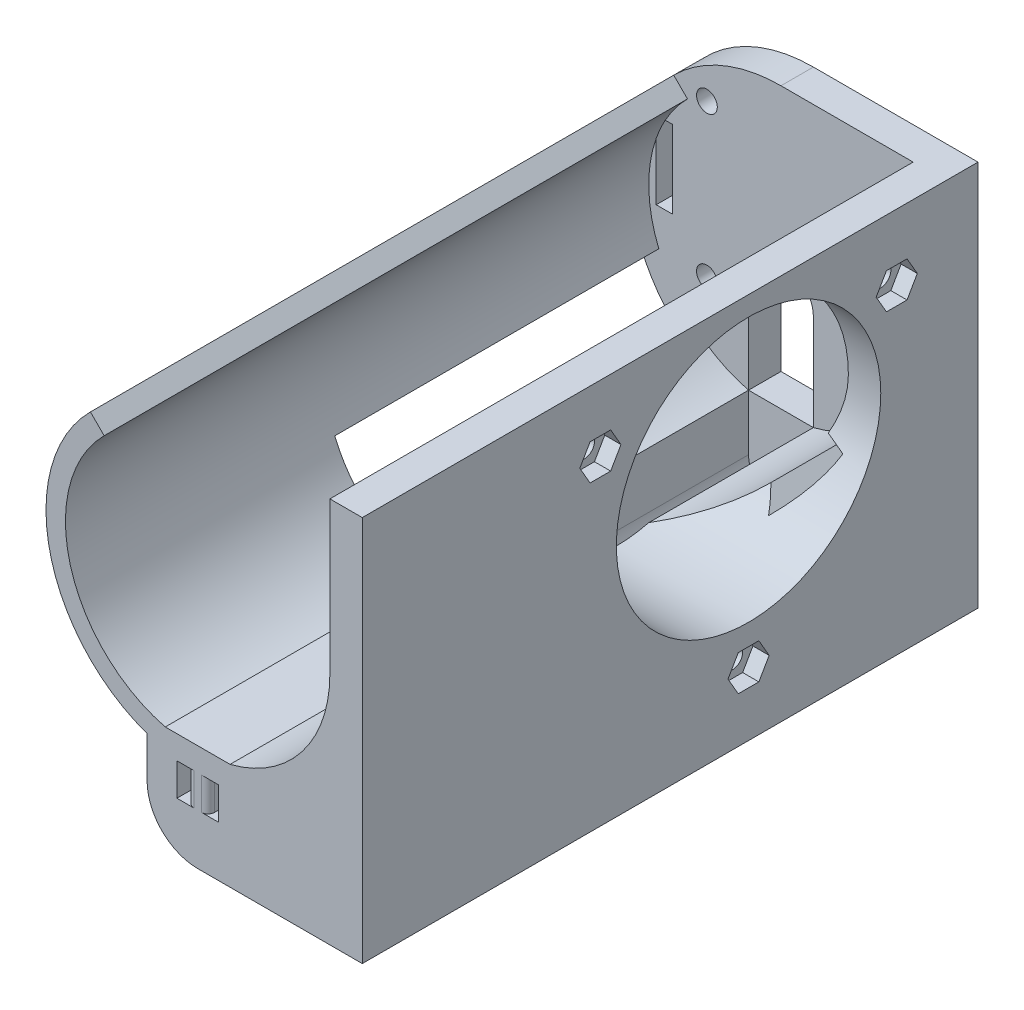
SolidWorks part; units mm, degrees
ref_plane "Front Plane" through (0, 0, 0) normal (0, 0, 1) x (1, 0, 0)
ref_plane "Top Plane" through (0, 0, 0) normal (0, 1, 0) x (1, 0, 0)
ref_plane "Right Plane" through (0, 0, 0) normal (1, 0, 0) x (0, 0, -1)
sketch "Sketch1" plane through (0, 0, 0) normal (0, 0, 1) x (1, 0, 0)
  line L0 (0, 20.4) -> (0, 23.4)
  line L1 (7.8067, 18.8471) -> (8.9548, 21.6188)
  line L2 (14.425, 14.425) -> (16.5463, 16.5463)
  line L3 (18.8471, 7.8067) -> (21.6188, 8.9548)
  line L4 (20.4, 0) -> (23.4, 0)
  line L5 (18.8471, -7.8067) -> (21.6188, -8.9548) [skipped]
  line L6 (14.425, -14.425) -> (16.5463, -16.5463) [skipped]
  line L7 (7.8067, -18.8471) -> (8.9548, -21.6188) [skipped]
  line L8 (0, -20.4) -> (0, -23.4) [skipped]
  line L9 (-7.8067, -18.8471) -> (-8.9548, -21.6188) [skipped]
  line L10 (-14.425, -14.425) -> (-16.5463, -16.5463) [skipped]
  line L11 (-18.8471, -7.8067) -> (-21.6188, -8.9548) [skipped]
  line L12 (-20.4, 0) -> (-23.4, 0)
  line L13 (-18.8471, 7.8067) -> (-21.6188, 8.9548)
  line L14 (-14.425, 14.425) -> (-16.5463, 16.5463)
  line L15 (-7.8067, 18.8471) -> (-8.9548, 21.6188)
  line L16 (-7.8, -28.4) -> (-7.8, -22.0617)
  line L18 (-5, -28.4) -> (-5, -19.7778)
  line L19 (5, -28.4) -> (5, -19.7778)
  line L21 (7.8, -28.4) -> (7.8, -22.0617)
  line L22 (-7.8, -36.2) -> (-7.8, -22.8596) construction
  line L23 (7.8, -36.2) -> (7.8, -22.8596) construction
  line L24 (-5, -33.4) -> (5, -33.4) construction
  line L25 (-5, -33.4) -> (-5, -22.8596) construction
  line L26 (5, -33.4) -> (5, -22.8596) construction
  line L27 (-7.8, -36.2) -> (7.8, -36.2) construction
  line L28 (7.8067, 18.8471) -> (8.9548, 21.6188) [skipped]
  line L29 (14.425, 14.425) -> (16.5463, 16.5463) [skipped]
  line L30 (18.8471, 7.8067) -> (21.6188, 8.9548) [skipped]
  line L31 (20.4, 0) -> (23.4, 0) [skipped]
  line L32 (18.8471, -7.8067) -> (21.6188, -8.9548)
  line L33 (14.425, -14.425) -> (16.5463, -16.5463)
  line L34 (7.8067, -18.8471) -> (8.9548, -21.6188)
  line L35 (0, -20.4) -> (0, -23.4)
  line L36 (-7.8067, -18.8471) -> (-8.9548, -21.6188)
  line L37 (-14.425, -14.425) -> (-16.5463, -16.5463)
  line L38 (-18.8471, -7.8067) -> (-21.6188, -8.9548)
  line L39 (-20.4, 0) -> (-23.4, 0) [skipped]
  line L40 (-18.8471, 7.8067) -> (-21.6188, 8.9548) [skipped]
  line L41 (-14.425, 14.425) -> (-16.5463, 16.5463) [skipped]
  line L42 (-7.8067, 18.8471) -> (-8.9548, 21.6188) [skipped]
  line L43 (-5, -19.7778) -> (5, -19.7778) construction
  line L44 (0, -19.7778) -> (0, -28.4) construction
  arc A0 (5, -19.7778) -> (-5, -19.7778) centre (0, 0) ccw
  arc A1 (7.8, -22.0617) -> (-7.8, -22.0617) centre (0, 0) ccw
  arc A2 (-5, -28.4) -> (5, -28.4) centre (0, -28.4) ccw
  arc A3 (-7.8, -28.4) -> (7.8, -28.4) centre (0, -28.4) ccw
  point P3 (7.8, -22.0617)
  point P6 (0, -23.4)
  point P7 (0, -20.4)
  point P33 (0, 0)
  point P40 (0, 0)
  point P45 (0, -33.4)
  point P54 (0, -28.4)
  point P55 (-5, -28.9793)
  point P56 (5, -28.9793)
  point P57 (-7.8, -22.0617)
  point P95 (0, 0)
  dimension "D1" = 40.8
  dimension "D2" = 46.8
  dimension "D6" = 10
  dimension "D4" = 2.8
  dimension "D5" = 16
  dimension "D8" = 10
  dimension "D9" = 8.6222
  dimension "D7" = 2.8
  dimension "D3" = 16
extrude "Boss-Extrude3" add sketch "Sketch1" along normal blind 40 contours L16 A3 L21 A1 L34 A0 L19 A2 L18 L36 | L34 A1 L33 A0 | L37 A1 L36 A0 | L12 A1 L38 A0 | L33 A1 L32 A0 | L32 A1 L4 A0 | L38 A1 L37 A0 region at (21.3748, -4.2517, 0) region at (-21.3748, -4.2517, 0) region at (18.1207, -12.1079, 0) region at (-18.1207, -12.1079, 0) region at (12.1079, -18.1207, 0) region at (-12.1079, -18.1207, 0) region at (8.1504, -20.3284, 0)
extrude "Boss-Extrude7" add sketch "Sketch1<12>" against normal blind 50 contours L34 A1 L33 A0 | L16 A3 L21 A1 L34 A0 L19 A2 L18 L36 | L12 A1 L38 A0 | L32 A1 L4 A0 | L37 A1 L36 A0 region at (21.3748, -4.2517, 0) region at (-21.3748, -4.2517, 0) region at (12.1079, -18.1207, 0) region at (-12.1079, -18.1207, 0) region at (8.1504, -20.3284, 0)
sketch "Sketch1<12>" plane through (0, 0, 0) normal (0, 0, 1) x (1, 0, 0) same geometry as "Sketch1"
sketch "Sketch3" plane through (0, 0, 40) normal (0, 0, 1) x (1, 0, 0)
  line L0 (-5, -19.7778) -> (5, -19.7778)
  line L1 (-5, -19.7778) -> (-5, -28.4)
  line L3 (5, -28.4) -> (5, -19.7778)
  line L9 (1.6, -23.4) -> (1.6, -28.4)
  line L13 (-1.6, -28.4) -> (-1.6, -23.4)
  line L14 (-1.6, -28.4) -> (-3.2, -28.4)
  line L15 (-1.6, -28.4) -> (-1.6, -23.4)
  line L16 (-1.6, -23.4) -> (-3.2, -23.4)
  line L17 (-3.2, -28.4) -> (-3.2, -23.4)
  line L18 (1.6, -28.4) -> (3.2, -28.4)
  line L19 (1.6, -28.4) -> (1.6, -23.4)
  line L20 (1.6, -23.4) -> (3.2, -23.4)
  line L21 (3.2, -28.4) -> (3.2, -23.4)
  arc A0 (-5, -28.4) -> (5, -28.4) centre (0, -28.4) ccw
  line M14 (5, -19.7778) -> (5, -28.4)
  arc M15 (5, -28.4) -> (-5, -28.4) centre (0, -28.4) cw
  line M16 (-5, -28.4) -> (-5, -19.7778)
  dimension "D1" = 10
  dimension "D5" = 1.6
  dimension "D6" = 1.6
extrude "Boss-Extrude8" add sketch "Sketch3" against normal blind 3 contours L0 L21 L18 L9 L20 L14 L17 L16 L13 M16 M15 M14 region at (0, -26.1315, 40)
sketch "Sketch5" plane through (0, 0, 37) normal (0, 0, -1) x (-1, 0, 0)
  line L0 (5, -28.4) -> (5, -19.7778) construction
  line L1 (-5, -19.7778) -> (5, -19.7778)
  line L2 (-5, -19.7778) -> (-5, -22.7778)
  line L3 (-5, -22.7778) -> (5, -22.7778)
  line L4 (5, -19.7778) -> (5, -22.7778)
  dimension "D1" = 10
  dimension "D2" = 3
extrude "Boss-Extrude9" add sketch "Sketch5" along normal blind 37
sketch "Sketch6" plane through (0, 0, 40) normal (0, 0, 1) x (1, 0, 0)
  line L0 (20.4, 0) -> (20.4, 23.4)
  line L1 (20.4, 23.4) -> (25.4, 23.4)
  line L2 (25.4, 23.4) -> (25.4, -36.2)
  line L4 (0, -36.2) -> (25.4, -36.2)
  line L5 (20.4, 0) -> (23.4, 0) construction
  line L6 (7.8, -28.4) -> (7.8, -22.0617) construction
  line L7 (20.4, 0) -> (23.4, 0)
  line L8 (7.8, -28.4) -> (7.8, -22.0617)
  arc A0 (-7.8, -28.4) -> (7.8, -28.4) centre (0, -28.4) ccw construction
  arc A1 (7.8, -22.0617) -> (-7.8, -22.0617) centre (0, 0) ccw construction
  arc A2 (7.8, -22.0617) -> (23.4, 0) centre (0, 0) ccw
  arc A3 (0, -36.2) -> (7.8, -28.4) centre (0, -28.4) ccw
  dimension "D1" = 5
extrude "Boss-Extrude10" add sketch "Sketch6" against normal up to surface (90 mm away) up to face at (0, -22.8562, -50)
sketch "Sketch8" plane through (0, 0, 0) normal (1, 0, 0) x (0, 0, -1)
  line L0 (-40, 0) -> (50, 0) construction
  line L2 (50, 0) -> (50, 23.4) construction
  line L3 (50, 23.4) -> (-40, 23.4) construction
  line L4 (39.0062, 23.4) -> (0.1938, 23.4)
  circle A0 centre (19.6, 0) radius 20.4
  circle A1 centre (19.6, 0) radius 30.4
  dimension "D1" = 40.8
  dimension "D2" = 10
extrude "Cut-Extrude1" cut sketch "Sketch8" along normal through all contours A0 region at (0, 0, -19.6)
sketch "Sketch9" plane through (25.4, 0, 0) normal (1, 0, 0) x (0, 0, -1)
  line L0 (19.6, 41.6909) -> (19.6, -54.0284) construction
  line L1 (-0.0876, 13.2) -> (-1.6754, 15.95)
  line L2 (22.7754, -26.4) -> (21.1877, -23.65)
  line L3 (21.1877, -23.65) -> (18.0123, -23.65)
  line L4 (18.0123, -23.65) -> (16.4246, -26.4)
  line L5 (16.4246, -26.4) -> (18.0123, -29.15)
  line L6 (18.0123, -29.15) -> (21.1877, -29.15)
  line L7 (21.1877, -29.15) -> (22.7754, -26.4)
  line L8 (-1.6754, 15.95) -> (-4.8508, 15.95)
  line L9 (-4.8508, 15.95) -> (-6.4385, 13.2)
  line L10 (-6.4385, 13.2) -> (-4.8508, 10.45)
  line L11 (-4.8508, 10.45) -> (-1.6754, 10.45)
  line L12 (-1.6754, 10.45) -> (-0.0876, 13.2)
  line L13 (40.8754, 10.45) -> (44.0508, 10.45)
  line L14 (44.0508, 10.45) -> (45.6385, 13.2)
  line L15 (45.6385, 13.2) -> (44.0508, 15.95)
  line L16 (44.0508, 15.95) -> (40.8754, 15.95)
  line L17 (40.8754, 15.95) -> (39.2876, 13.2)
  line L18 (39.2876, 13.2) -> (40.8754, 10.45)
  circle A0 centre (19.6, 0) radius 20.4 construction
  circle A1 centre (19.6, 0) radius 20.4
  circle A2 centre (19.6, -26.4) radius 2.75 construction
  dimension "D3" = 26.4
  dimension "D1" = 5.5
  dimension "D2" = 3
extrude "Cut-Extrude2" cut sketch "Sketch9" against normal blind 2.5 contours L6 L7 L2 L3 L4 L5 | L11 L12 L1 L8 L9 L10 | L17 L18 L13 L14 L15 L16 region at (25.4, 13.2, 3.2631) region at (25.4, -26.4, -19.6) region at (25.4, 13.2, -42.4631)
sketch "Sketch10" plane through (22.9, 0, 0) normal (1, 0, 0) x (0, 0, -1)
  line L0 (19.6, 40.3711) -> (19.6, -50.258) construction
  circle A0 centre (19.6, 0) radius 20.4 construction
  circle A1 centre (19.6, 0) radius 20.4
  circle A2 centre (19.6, -26.4) radius 1.6
  circle A3 centre (-3.2631, 13.2) radius 1.6
  circle A4 centre (42.4631, 13.2) radius 1.6
  dimension "D2" = 3.2
  dimension "D1" = 26.4
  dimension "D3" = 3
extrude "Cut-Extrude3" cut sketch "Sketch10" against normal up to surface (2.5 mm away) contours A2 L0 | L0 A2 | A3 | A4 region at (22.9, -26.4, -20.2791) region at (22.9, -26.4, -18.9209) region at (22.9, 13.2, 3.2631) region at (22.9, 13.2, -42.4631) up to face at (20.4, 11.2, -9.8667)
fillet "Fillet1" radius 1 6 edges at (1.6, -25.9, 40) (-1.6, -25.9, 40) (0, -22.7778, 37) (-5, -25.5889, 37) (0, -33.4, 37) (5, -25.5889, 37)
extrude "Boss-Extrude12" add sketch "Sketch1<13>" against normal up to surface (50 mm away) from surface contours L13 A1 L12 A0 | L14 A1 L13 A0 region at (-18.1207, 12.1079, 0) region at (-21.3748, 4.2517, 0) up to face at (-21.2728, -4.2314, -50) starting at face at (2.4617, -11.3637, 40)
sketch "Sketch1<13>" plane through (0, 0, 0) normal (0, 0, 1) x (1, 0, 0) same geometry as "Sketch1"
sketch "Sketch11" plane through (0, 0, -50) normal (0, 0, -1) x (-1, 0, 0)
  line L0 (14.425, 14.425) -> (16.5463, 16.5463) construction
  line L1 (14.425, 14.425) -> (16.5463, 16.5463)
  line L2 (-5, -19.7778) -> (-5, -5)
  line L3 (-5, -19.7778) -> (5, -19.7778)
  line L4 (5, -5) -> (5, -19.7778)
  line L5 (-20.4, 23.4) -> (0, 23.4)
  line L10 (-21.6188, -8.9548) -> (-18.8471, -7.8067)
  line L11 (-20.4, 0) -> (-20.4, 23.4)
  line L12 (-20.4, 23.4) -> (-25.4, 23.4)
  line L13 (-25.4, 23.4) -> (-25.4, -36.2)
  line L14 (-25.4, -36.2) -> (0, -36.2)
  line L15 (7.8, -28.4) -> (7.8, -22.0617)
  line L16 (16.5463, -16.5463) -> (14.425, -14.425)
  line L17 (5, -19.7778) -> (5, -28.4)
  line L18 (-5, -28.4) -> (-5, -19.7778)
  line L19 (-14.425, -14.425) -> (-16.5463, -16.5463)
  line L21 (-20.4, 0) -> (-20.4, 23.4)
  line L22 (-20.4, 23.4) -> (-25.4, 23.4)
  line L23 (-25.4, 23.4) -> (-25.4, -36.2)
  line L25 (7.8, -28.4) -> (7.8, -22.0617)
  line L27 (5, -19.7778) -> (5, -28.4)
  line L28 (-5, -28.4) -> (-5, -19.7778)
  line L35 (-25.4, -36.2) -> (0, -36.2)
  arc A0 (5, -19.7778) -> (-5, -19.7778) centre (0, 0) ccw construction
  arc A1 (5, -19.7778) -> (14.425, 14.425) centre (0, 0) ccw
  arc A2 (7.8, -22.0617) -> (-7.8, -22.0617) centre (0, 0) ccw construction
  arc A3 (7.8, -22.0617) -> (16.5463, 16.5463) centre (0, 0) ccw
  arc A4 (7.8, -22.0617) -> (-7.8, -22.0617) centre (0, 0) ccw
  arc A5 (-20.4, 0) -> (-5, -19.7778) centre (0, 0) ccw
  arc A6 (-5, -5) -> (5, -5) centre (0, -5) cw
  arc A7 (-20.4, 0) -> (-18.8471, -7.8067) centre (0, 0) ccw
  arc A8 (0, -36.2) -> (7.8, -28.4) centre (0, -28.4) ccw
  arc A9 (7.8, -22.0617) -> (16.5463, -16.5463) centre (0, 0) ccw
  arc A10 (5, -19.7778) -> (14.425, -14.425) centre (0, 0) ccw
  arc A11 (-5, -28.4) -> (5, -28.4) centre (0, -28.4) ccw
  arc A12 (-14.425, -14.425) -> (-5, -19.7778) centre (0, 0) ccw
  arc A13 (-21.6188, -8.9548) -> (-16.5463, -16.5463) centre (0, 0) ccw
  arc A14 (-20.4, 0) -> (-18.8471, -7.8067) centre (0, 0) ccw
  arc A15 (0, -36.2) -> (7.8, -28.4) centre (0, -28.4) ccw
  arc A16 (7.8, -22.0617) -> (16.5463, -16.5463) centre (0, 0) ccw
  arc A17 (5, -19.7778) -> (14.425, -14.425) centre (0, 0) ccw
  arc A18 (-5, -28.4) -> (5, -28.4) centre (0, -28.4) ccw
  arc A19 (-14.425, -14.425) -> (-5, -19.7778) centre (0, 0) ccw
  line M21 (-21.6188, -8.9548) -> (-18.8471, -7.8067)
  arc M22 (-18.8471, -7.8067) -> (-20.4, 0) centre (0, 0) cw
  line M23 (-20.4, 0) -> (-20.4, 23.4)
  line M24 (-20.4, 23.4) -> (-25.4, 23.4)
  line M25 (-25.4, 23.4) -> (-25.4, -36.2)
  arc M27 (0, -36.2) -> (7.8, -28.4) centre (0, -28.4) ccw
  line M28 (7.8, -28.4) -> (7.8, -22.0617)
  arc M29 (7.8, -22.0617) -> (16.5463, -16.5463) centre (0, 0) ccw
  line M30 (16.5463, -16.5463) -> (14.425, -14.425)
  arc M31 (14.425, -14.425) -> (5, -19.7778) centre (0, 0) cw
  line M32 (5, -19.7778) -> (5, -28.4)
  arc M33 (5, -28.4) -> (-5, -28.4) centre (0, -28.4) cw
  line M34 (-5, -28.4) -> (-5, -19.7778)
  arc M35 (-5, -19.7778) -> (-14.425, -14.425) centre (0, 0) cw
  line M36 (-14.425, -14.425) -> (-16.5463, -16.5463)
  arc M37 (-16.5463, -16.5463) -> (-21.6188, -8.9548) centre (0, 0) cw
  dimension "D1" = 0
extrude "Boss-Extrude13" add sketch "Sketch11" along normal blind 5 contours A4 L21 M24 M25 M27 M28 M29 M30 M31 M32 M33 M34 M35 M36 M37 | A4 M23 M21 M22 | L2 A6 L4 A1 L1 A4 A5 M31 M23 M22 M35 | A3 L1 A1 M30 | A5 M21 M37 M36 | L3 M34 M33 M32 | A4 L5 L21 region at (0.4143, 3.5154, -50) region at (-15.7281, 15.2432, -50) region at (14.1209, -19.1577, -50) region at (15.5956, 20.0575, -50) region at (0, -26.102, -50) region at (21.4848, -0.1814, -50) region at (18.1207, -12.1079, -50)
sketch "Sketch12" plane through (0, 0, -55) normal (0, 0, -1) x (-1, 0, 0)
  line L0 (-29.5217, -2.1278) -> (8.25, -2.1278) construction
  line L1 (8.25, 9.8722) -> (8.25, 11.5646) construction
  line L3 (-25.4, 23.4) -> (-25.4, -36.2) construction
  line L5 (-25.4, 23.4) -> (-25.4, -36.2) construction
  line L6 (8.25, 12.8722) -> (37.95, 12.8722)
  line L7 (8.25, -2.1278) -> (34.95, -2.1278)
  line L9 (8.25, 9.8722) -> (34.95, 9.8722)
  line L10 (34.95, -2.1278) -> (34.95, 9.8722)
  line L11 (37.95, -5.1278) -> (37.95, 12.8722)
  line L12 (8.25, -5.1278) -> (37.95, -5.1278)
  line L14 (8.25, 12.8722) -> (8.25, 9.8722)
  line L15 (5.25, 12.8722) -> (37.95, 12.8722) construction
  line L16 (5.25, -5.1278) -> (5.25, 12.8722) construction
  line L17 (5.25, -5.1278) -> (37.95, -5.1278) construction
  line L18 (8.25, -2.1278) -> (8.25, 9.8722) construction
  line L19 (8.25, -2.1278) -> (8.25, -5.1278)
  line L20 (-50.908, -19.7778) -> (36.0744, -19.7778) construction
  line L21 (13.0131, 12.8722) -> (14.6009, 15.6222)
  line L22 (14.6009, 15.6222) -> (13.0131, 18.3722)
  line L23 (13.0131, 18.3722) -> (9.8377, 18.3722)
  line L24 (9.8377, 18.3722) -> (8.25, 15.6222)
  line L25 (8.25, 15.6222) -> (9.8377, 12.8722)
  line L26 (9.8377, 12.8722) -> (13.0131, 12.8722)
  line L27 (13.0131, -10.6278) -> (14.6009, -7.8778)
  line L28 (14.6009, -7.8778) -> (13.0131, -5.1278)
  line L29 (13.0131, -5.1278) -> (9.8377, -5.1278)
  line L30 (9.8377, -5.1278) -> (8.25, -7.8778)
  line L31 (8.25, -7.8778) -> (9.8377, -10.6278)
  line L32 (9.8377, -10.6278) -> (13.0131, -10.6278)
  line L33 (16.75, 9.8722) -> (19.25, 9.8722)
  line L34 (16.75, 9.8722) -> (16.75, -2.1278)
  line L35 (16.75, -2.1278) -> (19.25, -2.1278)
  line L36 (19.25, 9.8722) -> (19.25, -2.1278)
  line L37 (5, -19.7778) -> (-5, -19.7778) construction
  circle A0 centre (11.4254, 15.6222) radius 2.75 construction
  circle A1 centre (11.4254, -7.8778) radius 2.75 construction
  circle A2 centre (11.4254, 15.6222) radius 1.6
  circle A3 centre (11.4254, -7.8778) radius 1.6
  dimension "D8" = 3.2
  dimension "D9" = 3.2
  dimension "D1" = 33.65
  dimension "D3" = 12
  dimension "D4" = 26.7
  dimension "D5" = 3
  dimension "D6" = 5.5
  dimension "D7" = 5.5
  dimension "D10" = 2.5
  dimension "D11" = 15.7
  dimension "D12" = 17.65
extrude "Cut-Extrude4" cut sketch "Sketch12" against normal blind 2.5 contours L24 L25 L6 L21 L22 L23 A2 | A2 | A3 | L31 L32 L27 L28 L12 L30 A3 region at (-9.1166, 14.2892, -55) region at (-13.7342, -6.5448, -55) region at (-11.4254, 15.6222, -55) region at (-11.4254, -7.8778, -55)
extrude "Cut-Extrude5" cut sketch "Sketch12<4>" against normal up to surface (5 mm away) contours A2 | A3 | L36 L9 L34 L7 region at (-18, 3.8722, -55) region at (-11.4254, 15.6222, -55) region at (-11.4254, -7.8778, -55) up to face at (0.3623, -3.6344, -50)
sketch "Sketch12<4>" plane through (0, 0, -55) normal (0, 0, -1) x (-1, 0, 0) same geometry as "Sketch12"
equation "\"tube end\"= 40"
equation "\"D1@Boss-Extrude3\"=\"tube end\""
equation "\"plunger travel\"= 50"
equation "\"D1@Boss-Extrude7\"=\"plunger travel\""
